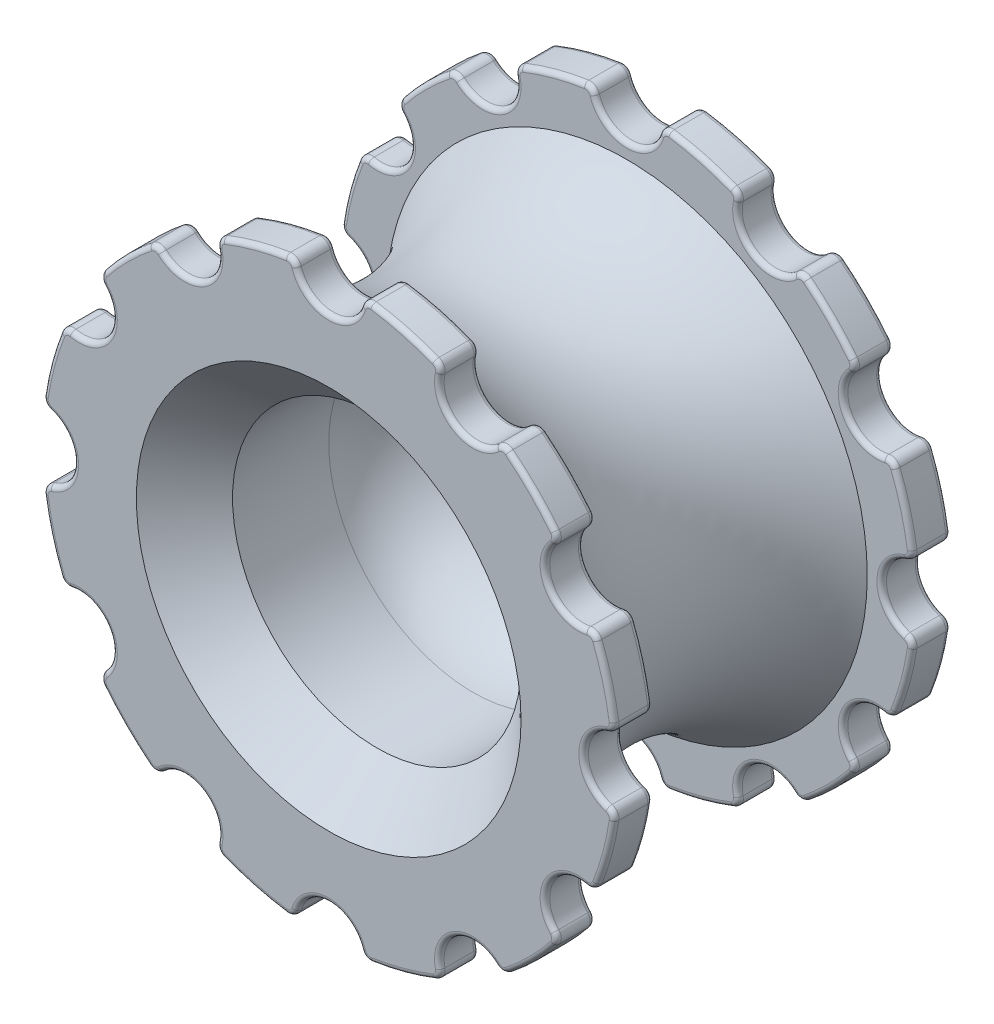
SolidWorks part; units mm, degrees
ref_plane "Спереди" through (0, 0, 0) normal (0, 0, 1) x (1, 0, 0)
ref_plane "Сверху" through (0, 0, 0) normal (0, 1, 0) x (1, 0, 0)
ref_plane "Справа" through (0, 0, 0) normal (1, 0, 0) x (0, 0, -1)
sketch "Эскиз1" plane through (0, 0, 0) normal (0, 0, 1) x (1, 0, 0)
  line L0 (0, -796.897) -> (0, 39047.9522) construction
  circle A0 centre (0, 0) radius 30 construction
  arc A1 (-3.494, 29.7958) -> (3.494, 29.7958) centre (0, 30) ccw
  arc A2 (3.494, 29.7958) -> (11.872, 27.551) centre (0, 0) cw
  arc A3 (11.872, 27.551) -> (17.9238, 24.0569) centre (15, 25.9808) ccw
  arc A4 (17.9238, 24.0569) -> (24.0569, 17.9238) centre (0, 0) cw
  arc A5 (24.0569, 17.9238) -> (27.551, 11.872) centre (25.9808, 15) ccw
  arc A6 (27.551, 11.872) -> (29.7958, 3.494) centre (0, 0) cw
  arc A7 (29.7958, 3.494) -> (29.7958, -3.494) centre (30, 0) ccw
  arc A8 (29.7958, -3.494) -> (27.551, -11.872) centre (0, 0) cw
  arc A9 (27.551, -11.872) -> (24.0569, -17.9238) centre (25.9808, -15) ccw
  arc A10 (24.0569, -17.9238) -> (17.9238, -24.0569) centre (0, 0) cw
  arc A11 (17.9238, -24.0569) -> (11.872, -27.551) centre (15, -25.9808) ccw
  arc A12 (11.872, -27.551) -> (3.494, -29.7958) centre (0, 0) cw
  arc A13 (3.494, -29.7958) -> (-3.494, -29.7958) centre (0, -30) ccw
  arc A14 (-3.494, -29.7958) -> (-11.872, -27.551) centre (0, 0) cw
  arc A15 (-11.872, -27.551) -> (-17.9238, -24.0569) centre (-15, -25.9808) ccw
  arc A16 (-17.9238, -24.0569) -> (-24.0569, -17.9238) centre (0, 0) cw
  arc A17 (-24.0569, -17.9238) -> (-27.551, -11.872) centre (-25.9808, -15) ccw
  arc A18 (-27.551, -11.872) -> (-29.7958, -3.494) centre (0, 0) cw
  arc A19 (-29.7958, -3.494) -> (-29.7958, 3.494) centre (-30, 0) ccw
  arc A20 (-29.7958, 3.494) -> (-27.551, 11.872) centre (0, 0) cw
  arc A21 (-27.551, 11.872) -> (-24.0569, 17.9238) centre (-25.9808, 15) ccw
  arc A22 (-24.0569, 17.9238) -> (-17.9238, 24.0569) centre (0, 0) cw
  arc A23 (-17.9238, 24.0569) -> (-11.872, 27.551) centre (-15, 25.9808) ccw
  arc A24 (-11.872, 27.551) -> (-3.494, 29.7958) centre (0, 0) cw
  point P55 (0, 0)
  dimension "D1" = 3.5
  dimension "D2" = 0
  dimension "D3" = 30
  dimension "D4" = 12
  dimension "D5" = 60
extrude "Бобышка-Вытянуть1" add sketch "Эскиз1" along normal blind 35
fillet "Скругление1" radius 1 24 edges at (3.494, 29.7958, 17.5) (11.872, 27.551, 17.5) (17.9238, 24.0569, 17.5) (29.7958, 3.494, 17.5) (27.551, 11.872, 17.5) (24.0569, 17.9238, 17.5) (29.7958, -3.494, 17.5) (27.551, -11.872, 17.5) (17.9238, -24.0569, 17.5) (24.0569, -17.9238, 17.5) (11.872, -27.551, 17.5) (-11.872, -27.551, 17.5) (3.494, -29.7958, 17.5) (-3.494, -29.7958, 17.5) (-17.9238, -24.0569, 17.5) (-24.0569, -17.9238, 17.5) (-27.551, -11.872, 17.5) (-29.7958, -3.494, 17.5) (-29.7958, 3.494, 17.5) (-27.551, 11.872, 17.5) (-24.0569, 17.9238, 17.5) (-17.9238, 24.0569, 17.5) (-11.872, 27.551, 17.5) (-3.494, 29.7958, 17.5)
sketch "Эскиз2" plane through (0, 0, 0) normal (0, 1, 0) x (1, 0, 0)
  line L0 (0, -1000) -> (0, 49000) construction
  line L2 (-30, -4) -> (-30, -31)
  line L5 (-30, -4) -> (-25, -4)
  line L6 (-30, -31) -> (-25, -31)
  arc A1 (-25, -4) -> (-25, -31) centre (-39.7564, -17.5) cw
  dimension "D3" = 5
  dimension "D5" = 20
  dimension "D1" = 4
  dimension "D2" = 27
  dimension "D4" = 30
revolve "Вырез-Повернуть1" cut sketch "Эскиз2" angle 360 about L0
sketch "Эскиз3" plane through (0, 0, 35) normal (0, 0, 1) x (1, 0, 0)
  circle A0 centre (0, 0) radius 15
  dimension "D1" = 30
extrude "Вырез-Вытянуть1" cut sketch "Эскиз3" against normal blind 25
fillet "Скругление2" radius 0.5 192 edges at (-29.5254, -3.7689, 4) (-26.5, 0, 4) (-29.5254, 3.7689, 4) (-28.9778, 7.7646, 4) (-27.4542, 11.4987, 4) (-22.9497, 13.25, 4) (-23.6853, 18.0266, 4) (-21.2132, 21.2132, 4) (-18.0266, 23.6853, 4) (-13.25, 22.9497, 4) (-11.4987, 27.4542, 4) (-7.7646, 28.9778, 4) (-3.7689, 29.5254, 4) (0, 26.5, 4) (3.7689, 29.5254, 4) (7.7646, 28.9778, 4) (11.4987, 27.4542, 4) (13.25, 22.9497, 4) (18.0266, 23.6853, 4) (21.2132, 21.2132, 4) (23.6853, 18.0266, 4) (22.9497, 13.25, 4) (27.4542, 11.4987, 4) (28.9778, 7.7646, 4) (29.5254, 3.7689, 4) (26.5, 0, 4) (29.5254, -3.7689, 4) (28.9778, -7.7646, 4) (27.4542, -11.4987, 4) (22.9497, -13.25, 4) (23.6853, -18.0266, 4) (21.2132, -21.2132, 4) (18.0266, -23.6853, 4) (13.25, -22.9497, 4) (11.4987, -27.4542, 4) (7.7646, -28.9778, 4) (3.7689, -29.5254, 4) (0, -26.5, 4) (-3.7689, -29.5254, 4) (-7.7646, -28.9778, 4) (-11.4987, -27.4542, 4) (-13.25, -22.9497, 4) (-18.0266, -23.6853, 4) (-21.2132, -21.2132, 4) (-23.6853, -18.0266, 4) (-22.9497, -13.25, 4) (-27.4542, -11.4987, 4) (-29.5254, -3.7689, 31) (-26.5, 0, 31) (-29.5254, 3.7689, 31) (-28.9778, 7.7646, 31) (-27.4542, 11.4987, 31) (-22.9497, 13.25, 31) (-23.6853, 18.0266, 31) (-21.2132, 21.2132, 31) (-18.0266, 23.6853, 31) (-13.25, 22.9497, 31) (-11.4987, 27.4542, 31) (-7.7646, 28.9778, 31) (-3.7689, 29.5254, 31) (0, 26.5, 31) (3.7689, 29.5254, 31) (7.7646, 28.9778, 31) (11.4987, 27.4542, 31) (13.25, 22.9497, 31) (18.0266, 23.6853, 31) (21.2132, 21.2132, 31) (23.6853, 18.0266, 31) (22.9497, 13.25, 31) (27.4542, 11.4987, 31) (28.9778, 7.7646, 31) (29.5254, 3.7689, 31) (26.5, 0, 31) (29.5254, -3.7689, 31) (28.9778, -7.7646, 31) (27.4542, -11.4987, 31) (22.9497, -13.25, 31) (23.6853, -18.0266, 31) (21.2132, -21.2132, 31) (18.0266, -23.6853, 31) (13.25, -22.9497, 31) (11.4987, -27.4542, 31) (7.7646, -28.9778, 31) (3.7689, -29.5254, 31) (0, -26.5, 31) (-3.7689, -29.5254, 31) (-7.7646, -28.9778, 31) (-11.4987, -27.4542, 31) (-13.25, -22.9497, 31) (-18.0266, -23.6853, 31) (-21.2132, -21.2132, 31) (-23.6853, -18.0266, 31) (-22.9497, -13.25, 31) (-27.4542, -11.4987, 31) (-29.5254, 3.7689, 35) (-28.9778, 7.7646, 35) (-27.4542, 11.4987, 35) (-22.9497, 13.25, 35) (-23.6853, 18.0266, 35) (-21.2132, 21.2132, 35) (-18.0266, 23.6853, 35) (-13.25, 22.9497, 35) (-11.4987, 27.4542, 35) (-7.7646, 28.9778, 35) (-3.7689, 29.5254, 35) (0, 26.5, 35) (3.7689, 29.5254, 35) (7.7646, 28.9778, 35) (11.4987, 27.4542, 35) (13.25, 22.9497, 35) (18.0266, 23.6853, 35) (21.2132, 21.2132, 35) (23.6853, 18.0266, 35) (22.9497, 13.25, 35) (27.4542, 11.4987, 35) (28.9778, 7.7646, 35) (29.5254, 3.7689, 35) (26.5, 0, 35) (29.5254, -3.7689, 35) (28.9778, -7.7646, 35) (27.4542, -11.4987, 35) (22.9497, -13.25, 35) (23.6853, -18.0266, 35) (21.2132, -21.2132, 35) (18.0266, -23.6853, 35) (13.25, -22.9497, 35) (11.4987, -27.4542, 35) (7.7646, -28.9778, 35) (3.7689, -29.5254, 35) (0, -26.5, 35) (-3.7689, -29.5254, 35) (-7.7646, -28.9778, 35) (-11.4987, -27.4542, 35) (-13.25, -22.9497, 35) (-18.0266, -23.6853, 35) (-21.2132, -21.2132, 35) (-23.6853, -18.0266, 35) (-22.9497, -13.25, 35) (-27.4542, -11.4987, 35) (-28.9778, -7.7646, 35) (-29.5254, -3.7689, 35) (3.7689, 29.5254, 0) (0, 26.5, 0) (-3.7689, 29.5254, 0) (-7.7646, 28.9778, 0) (-11.4987, 27.4542, 0) (-13.25, 22.9497, 0) (-18.0266, 23.6853, 0) (-21.2132, 21.2132, 0) (-23.6853, 18.0266, 0) (-22.9497, 13.25, 0) (-27.4542, 11.4987, 0) (-28.9778, 7.7646, 0) (-29.5254, 3.7689, 0) (-26.5, 0, 0) (-29.5254, -3.7689, 0) (-28.9778, -7.7646, 0) (-27.4542, -11.4987, 0) (-22.9497, -13.25, 0) (-23.6853, -18.0266, 0) (-21.2132, -21.2132, 0) (-18.0266, -23.6853, 0) (-13.25, -22.9497, 0) (-11.4987, -27.4542, 0) (-7.7646, -28.9778, 0) (-3.7689, -29.5254, 0) (0, -26.5, 0) (3.7689, -29.5254, 0) (7.7646, -28.9778, 0) (11.4987, -27.4542, 0) (13.25, -22.9497, 0) (18.0266, -23.6853, 0) (21.2132, -21.2132, 0) (23.6853, -18.0266, 0) (22.9497, -13.25, 0) (27.4542, -11.4987, 0) (28.9778, -7.7646, 0) (29.5254, -3.7689, 0) (26.5, 0, 0) (29.5254, 3.7689, 0) (28.9778, 7.7646, 0) (27.4542, 11.4987, 0) (22.9497, 13.25, 0) (23.6853, 18.0266, 0) (21.2132, 21.2132, 0) (18.0266, 23.6853, 0) (13.25, 22.9497, 0) (11.4987, 27.4542, 0) (7.7646, 28.9778, 0) (-28.9778, -7.7646, 4) (-28.9778, -7.7646, 31) (-26.5, 0, 35)
fillet "Скругление3" radius 10 1 edges at (15, 0, 10)
chamfer "Фаска1" distance 5 angle 45 1 edges at (15, 0, 35)
sketch "Эскиз4" plane through (0, 0, 0) normal (0, 0, -1) x (-1, 0, 0)
  circle A0 centre (0, 0) radius 6
  dimension "D1" = 12
extrude "Бобышка-Вытянуть2" add sketch "Эскиз4" along normal blind 1
sketch "Эскиз5" plane through (0, 0, -1) normal (0, 0, -1) x (-1, 0, 0)
  circle A0 centre (0, 0) radius 4.75
  dimension "D1" = 9.5
extrude "Бобышка-Вытянуть3" add sketch "Эскиз5" along normal blind 4.25
sketch "Эскиз6" plane through (0, 0, -5.25) normal (0, 0, -1) x (-1, 0, 0)
  circle A0 centre (0, 0) radius 1.5
  dimension "D1" = 3
extrude "Вырез-Вытянуть2" cut sketch "Эскиз6" against normal blind 38
